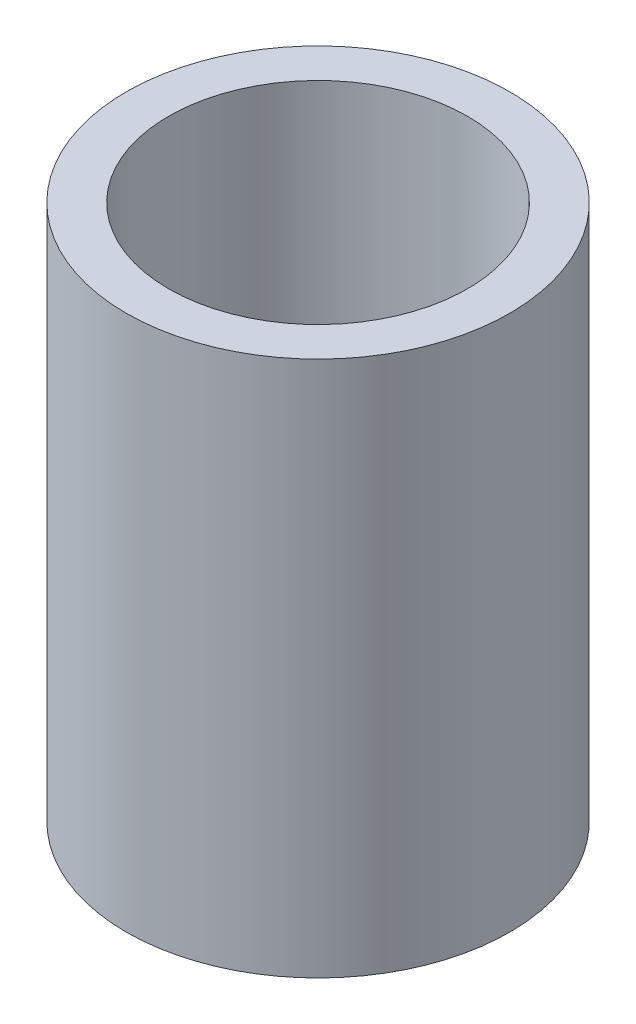
SolidWorks part; units mm, degrees
ref_plane "Front Plane" through (0, 0, 0) normal (0, 0, 1) x (1, 0, 0)
ref_plane "Top Plane" through (0, 0, 0) normal (0, 1, 0) x (1, 0, 0)
ref_plane "Right Plane" through (0, 0, 0) normal (1, 0, 0) x (0, 0, -1)
sketch "Sketch1" plane through (0, 0, 0) normal (0, 1, 0) x (1, 0, 0)
  circle A0 centre (0, 0) radius 22.5
  dimension "SLEEVE_OD" = 45
extrude "Boss-Extrude1" add sketch "Sketch1" along normal blind 62.8766
sketch "Sketch2" plane through (0, 0, 0) normal (0, 1, 0) x (1, 0, 0)
  circle A0 centre (0, 0) radius 17.5354
  dimension "BORE_D" = 35.0709
extrude "Cut-Extrude1" cut sketch "Sketch2" along normal through all
chamfer "Chamfer1" distance 3.059 angle 45 rebuild error yes
